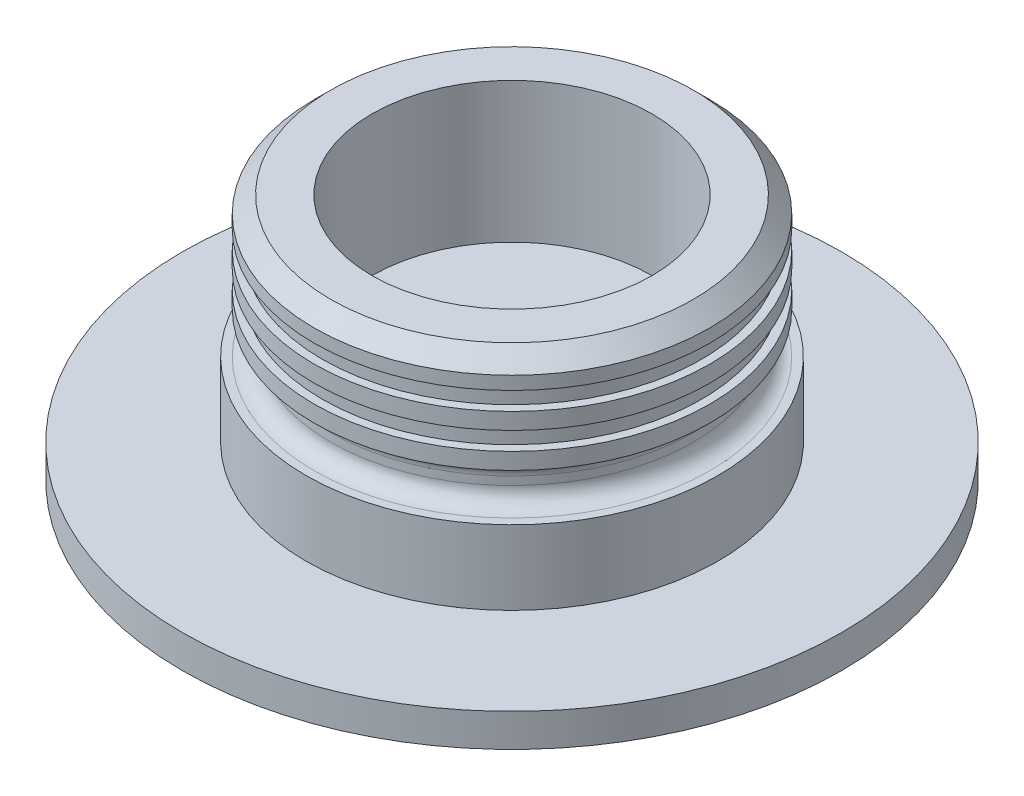
SolidWorks part; units mm, degrees
ref_plane "Front Plane" through (0, 0, 0) normal (0, 0, 1) x (1, 0, 0)
ref_plane "Top Plane" through (0, 0, 0) normal (0, 1, 0) x (1, 0, 0)
ref_plane "Right Plane" through (0, 0, 0) normal (1, 0, 0) x (0, 0, -1)
sketch "Sketch1" plane through (0, 0, 0) normal (0, 1, 0) x (1, 0, 0)
  circle A0 centre (0, 0) radius 40
  circle A1 centre (0, 0) radius 2.1
  dimension "D1" = 80
  dimension "D2" = 4.2
extrude "Boss-Extrude1" add sketch "Sketch1" along normal blind 4
sketch "Sketch2" plane through (0, 4, 0) normal (0, 1, 0) x (1, 0, 0)
  circle A0 centre (0, 0) radius 6.1
  circle A5 centre (0, 0) radius 25
  dimension "D1" = 12.2
  dimension "D6" = 50
extrude "Boss-Extrude5" add sketch "Sketch2" along normal blind 9
sketch "Sketch6" plane through (0, 13, 0) normal (0, 1, 0) x (1, 0, 0)
  circle A0 centre (0, 0) radius 22
  circle A1 centre (0, 0) radius 17
  circle A2 centre (0, 0) radius 25 construction
  dimension "D1" = 3
  dimension "D2" = 5
extrude "Boss-Extrude6" add sketch "Sketch6" along normal blind 5
sketch "Sketch7" plane through (0, 18, 0) normal (0, 1, 0) x (1, 0, 0)
  circle A0 centre (0, 0) radius 24
  circle A1 centre (0, 0) radius 17
  circle A3 centre (0, 0) radius 17 construction
  circle A4 centre (0, 0) radius 22 construction
  dimension "D1" = 2
extrude "Boss-Extrude7" add sketch "Sketch7" along normal blind 12
sketch "Sketch9" plane through (0, 0, 0) normal (1, 0, 0) x (0, 0, -1)
  line L0 (-24, 30) -> (-24, 18) construction
  line L1 (-24, 18) -> (24, 18) construction
  line L2 (-24, 26.4) -> (-23, 26.4)
  line L3 (-24, 26.4) -> (-24, 24.2)
  line L4 (-24, 24.2) -> (-23, 24.2)
  line L5 (-23, 26.4) -> (-23, 24.2)
  line L6 (-24, 22.2) -> (-23, 22.2)
  line L7 (-24, 22.2) -> (-24, 20)
  line L8 (-24, 20) -> (-23, 20)
  line L9 (-23, 22.2) -> (-23, 20)
  line L10 (0, 0) -> (0, 30) construction
  line L11 (17, 30) -> (-17, 30) construction
  circle A0 centre (-24, 21.1) radius 1 construction
  circle A1 centre (-24, 25.3) radius 1 construction
  point P15 (-23, 25.3)
  point P17 (-23, 21.1)
  dimension "D1" = 2
  dimension "D2" = 2
  dimension "D3" = 2.2
  dimension "D4" = 2.2
  dimension "D5" = 2
  dimension "D6" = 2
revolve "Cut-Revolve1" cut sketch "Sketch9" angle 360 about L10
chamfer "Chamfer1" distance 2 angle 45 1 edges at (0, 30, 24)
fillet "Fillet1" radius 2 2 edges at (0, 13, 22) (0, 18, 22)
